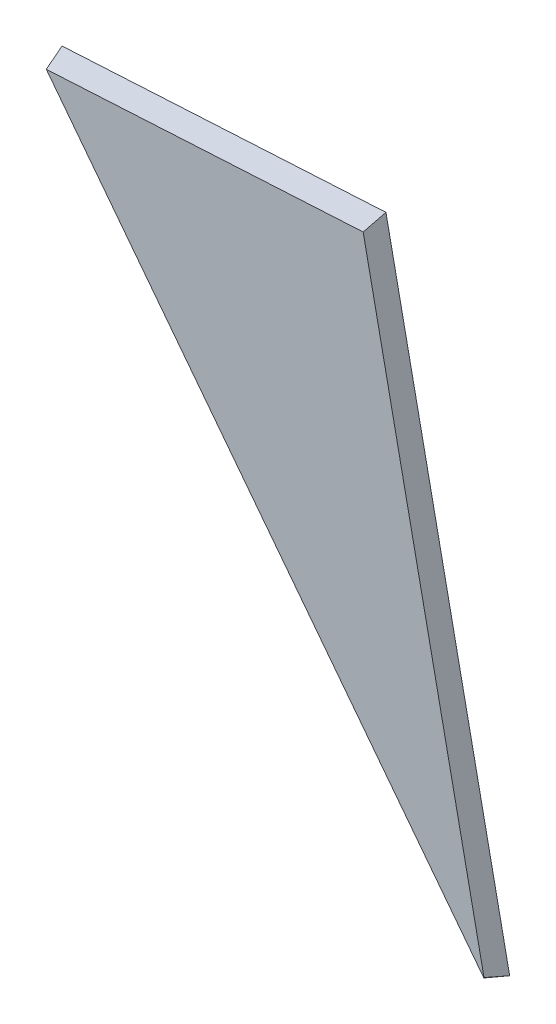
SolidWorks part; units mm, degrees
ref_plane "Спереди" through (0, 0, 0) normal (0, 0, 1) x (1, 0, 0)
ref_plane "Сверху" through (0, 0, 0) normal (0, 1, 0) x (1, 0, 0)
ref_plane "Справа" through (0, 0, 0) normal (1, 0, 0) x (0, 0, -1)
sketch "Эскиз1" plane through (0, 0, 0) normal (0, 0, 1) x (1, 0, 0)
  line L0 (-849.5899, 515.839) -> (787.506, 606.4051)
  line L1 (787.506, 606.4051) -> (281.6156, -953.1975)
  line L2 (281.6156, -953.1975) -> (-849.5899, 515.839)
extrude "Бобышка-Вытянуть1" add sketch "Эскиз1" along normal blind 60
chamfer "Chamfer3" distance 60 angle 11.23 1 edges at (-31.0419, 561.122, 60) first distance on face at (-31.0419, 561.122, 30)
chamfer "Chamfer4" distance 60 angle 11.23 1 edges at (532.5904, -179.4708, 60) first distance on face at (533.5756, -176.4335, 30)
chamfer "Chamfer5" distance 60 angle 9.015 1 edges at (-283.9872, -218.6793, 60) first distance on face at (-283.9872, -218.6793, 30)
sketch "Sketch1" plane through (0, 0, 0) normal (0, 0, -1) x (-1, 0, 0)
  line L0 (31.0419, 561.122) -> (-281.6156, -953.1975)
  line L1 (-787.506, 606.4051) -> (849.5899, 515.839) construction
  line L2 (-281.6156, -953.1975) -> (-787.506, 606.4051) construction
  line L3 (-281.6156, -953.1975) -> (-787.506, 606.4051)
  line L4 (-787.506, 606.4051) -> (31.0419, 561.122)
extrude "Cut-Extrude1" cut sketch "Sketch1" against normal through all
equation "\"D1@Бобышка-Вытянуть1\" = \"THI@Geocorkwithdoor1.0.Assembly\""
equation "\"D2@Chamfer3\" = \"ABchanferAngle@Geocorkwithdoor1.0.Assembly\""
equation "\"D2@Chamfer4\" = \"ABchanferAngle@Geocorkwithdoor1.0.Assembly\""
equation "\"DC1@Chamfer\" = \"THI@Geocorkwithdoor1.0.Assembly\""
equation "\"DC2@Chamfer\" = \"AAchanferangle@Geocorkwithdoor1.0.Assembly\""
equation "\"DC2@Chamfer\" = \"ABchanferAngle@Geocorkwithdoor1.0.Assembly\""
